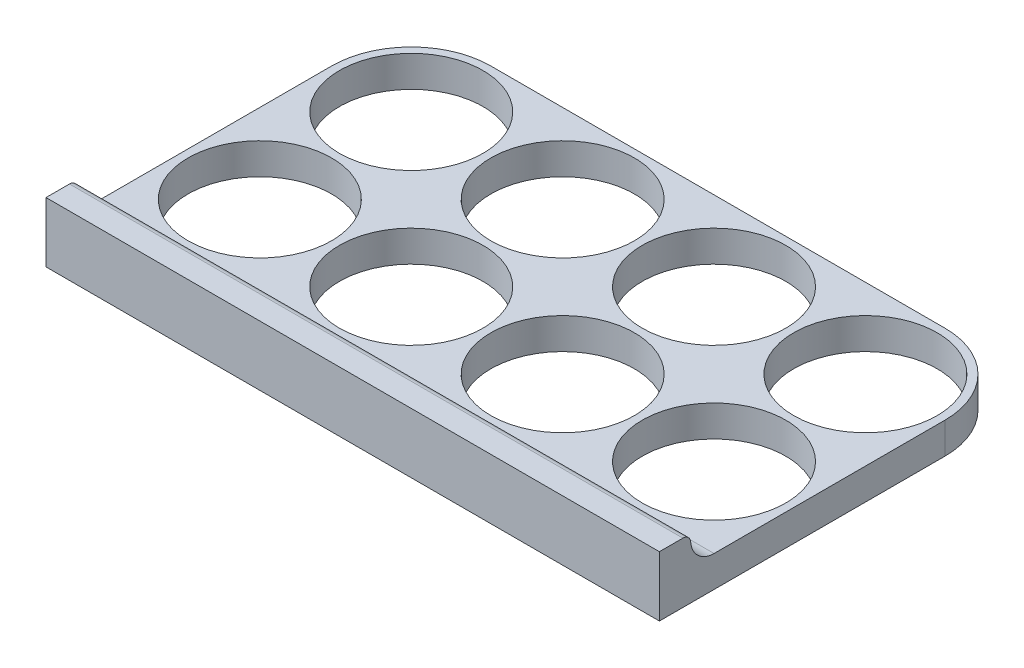
SolidWorks part; units mm, degrees
ref_plane "Front Plane" through (0, 0, 0) normal (0, 0, 1) x (1, 0, 0)
ref_plane "Top Plane" through (0, 0, 0) normal (0, 1, 0) x (1, 0, 0)
ref_plane "Right Plane" through (0, 0, 0) normal (1, 0, 0) x (0, 0, -1)
sketch "Sketch1" plane through (0, 0, 0) normal (0, 1, 0) x (1, 0, 0)
  line L0 (0, 0) -> (58.2, 0) construction
  line L1 (0, 19.4) -> (58.2, 19.4) construction
  line L2 (0, 0) -> (58.2, 19.4) construction
  line L3 (-10.2, 0) -> (-10.2, -17.2)
  line L5 (-10.2, 0) -> (-10.2, 19.4)
  line L6 (0, 29.6) -> (58.2, 29.6)
  line L7 (68.4, 0) -> (68.4, 19.4)
  line L8 (29.1, 29.6) -> (29.1, -9.2) construction
  line L9 (-10.2, 9.7) -> (68.4, 9.7) construction
  line L10 (-10.2, -17.2) -> (68.4, -17.2)
  line L11 (68.4, -17.2) -> (68.4, 0)
  line L12 (0, -9.2) -> (58.2, -9.2) construction
  circle A0 centre (0, 0) radius 9.2
  circle A1 centre (19.4, 0) radius 9.2
  circle A2 centre (38.8, 0) radius 9.2
  circle A3 centre (58.2, 0) radius 9.2
  circle A4 centre (19.4, 19.4) radius 9.2
  circle A5 centre (38.8, 19.4) radius 9.2
  circle A6 centre (58.2, 19.4) radius 9.2
  circle A7 centre (0, 19.4) radius 9.2
  arc A10 (58.2, 29.6) -> (68.4, 19.4) centre (58.2, 19.4) cw
  arc A11 (-10.2, 19.4) -> (0, 29.6) centre (0, 19.4) cw
  point P3 (29.1, 9.7)
  point P4 (29.1, 9.7)
  point P22 (0, 28.6)
  point P25 (68.4, -10.2)
  point P31 (68.4, 29.6)
  point P34 (-10.2, 29.6)
  dimension "D1" = 18.4
  dimension "D2" = 4
  dimension "D4" = 19.4
  dimension "D5" = 19.4
  dimension "D6" = 19.4
  dimension "D8" = 78.6
  dimension "D10" = 8
  dimension "D3" = 2
extrude "Boss-Extrude1" add sketch "Sketch1" along normal blind 4
sketch "Sketch2" plane through (0, 4, 0) normal (0, 1, 0) x (1, 0, 0)
  line L0 (68.4, -17.2) -> (68.4, 19.4) construction
  line L1 (-10.2, -17.2) -> (68.4, -17.2)
  line L2 (-10.2, -17.2) -> (-10.2, -13.2)
  line L3 (-10.2, -13.2) -> (68.4, -13.2)
  line L4 (68.4, -17.2) -> (68.4, -13.2)
  dimension "D1" = 4
extrude "Boss-Extrude2" add sketch "Sketch2" along normal blind 3.7
ref_plane "Plane1" through (29.1, 0, 0) normal (1, 0, 0) x (0, 0, -1)
fillet "Fillet1" radius 3 1 edges at (29.1, 4, 13.2)
fillet "Fillet2" radius 1 1 edges at (29.1, 7.7, 13.2)
